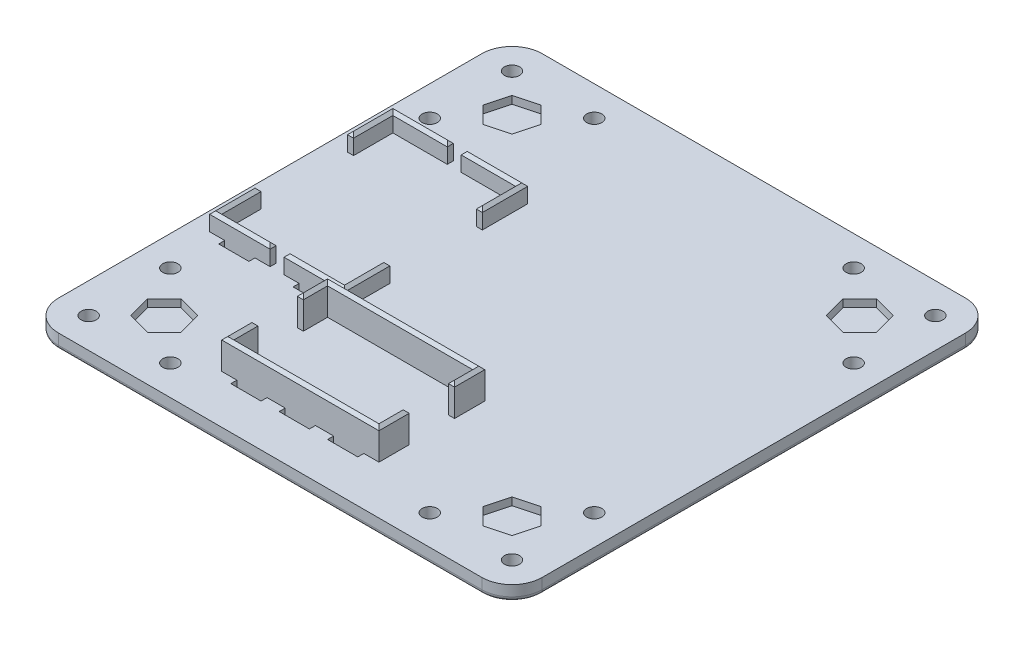
SolidWorks part; units mm, degrees
ref_plane "Front Plane" through (0, 0, 0) normal (0, 0, 1) x (1, 0, 0)
ref_plane "Top Plane" through (0, 0, 0) normal (0, 1, 0) x (1, 0, 0)
ref_plane "Right Plane" through (0, 0, 0) normal (1, 0, 0) x (0, 0, -1)
sketch "Sketch1" plane through (0, 0, 0) normal (0, 1, 0) x (1, 0, 0)
  line L1 (0, 0) -> (203.2, 0)
  line L2 (0, 0) -> (0, 203.2)
  line L3 (0, 203.2) -> (203.2, 203.2)
  line L4 (203.2, 0) -> (203.2, 203.2)
  dimension "D1" = 203.2
  dimension "D2" = 203.2
extrude "Boss-Extrude1" add sketch "Sketch1" along normal blind 6.35
fillet "Fillet1" radius 12.7 4 edges at (0, 3.175, -203.2) (0, 3.175, 0) (203.2, 3.175, 0) (203.2, 3.175, -203.2)
sketch "Sketch2" plane through (0, 0, 0) normal (0, -1, 0) x (1, 0, 0)
  circle A0 centre (12.7, -12.7) radius 3.175
  circle A1 centre (190.5, -12.7) radius 3.175
  circle A2 centre (190.5, -190.5) radius 3.175
  circle A3 centre (12.7, -190.5) radius 3.175
  arc A4 (190.5, -203.2) -> (203.2, -190.5) centre (190.5, -190.5) ccw construction
  arc A5 (12.7, 0) -> (0, -12.7) centre (12.7, -12.7) ccw construction
  dimension "D1" = 6.35
extrude "Cut-Extrude1" cut sketch "Sketch2" against normal through all
sketch "Sketch22" plane through (0, 6.35, 0) normal (0, 1, 0) x (1, 0, 0)
  line L17 (190.5, 203.2) -> (12.7, 203.2) construction
  line L18 (203.2, 12.7) -> (203.2, 190.5) construction
  line L21 (181.6542, 181.6542) -> (172.0521, 184.2271)
  line L22 (172.0521, 184.2271) -> (165.0229, 177.1979)
  line L23 (165.0229, 177.1979) -> (167.5958, 167.5958)
  line L24 (167.5958, 167.5958) -> (177.1979, 165.0229)
  line L25 (177.1979, 165.0229) -> (184.2271, 172.0521)
  line L26 (184.2271, 172.0521) -> (181.6542, 181.6542)
  line L27 (174.625, 174.625) -> (190.5, 190.5) construction
  line L28 (101.6, 203.2) -> (101.6, 0) construction
  line L29 (12.7, 0) -> (190.5, 0) construction
  line L30 (203.2, 101.6) -> (0, 101.6) construction
  line L31 (0, 190.5) -> (0, 12.7) construction
  line L32 (28.575, 174.625) -> (12.7, 190.5) construction
  line L33 (18.9729, 172.0521) -> (21.5458, 181.6542)
  line L34 (26.0021, 165.0229) -> (18.9729, 172.0521)
  line L35 (35.6042, 167.5958) -> (26.0021, 165.0229)
  line L36 (38.1771, 177.1979) -> (35.6042, 167.5958)
  line L37 (31.1479, 184.2271) -> (38.1771, 177.1979)
  line L38 (21.5458, 181.6542) -> (31.1479, 184.2271)
  line L39 (174.625, 28.575) -> (190.5, 12.7) construction
  line L40 (184.2271, 31.1479) -> (181.6542, 21.5458)
  line L41 (177.1979, 38.1771) -> (184.2271, 31.1479)
  line L42 (167.5958, 35.6042) -> (177.1979, 38.1771)
  line L43 (165.0229, 26.0021) -> (167.5958, 35.6042)
  line L44 (172.0521, 18.9729) -> (165.0229, 26.0021)
  line L45 (181.6542, 21.5458) -> (172.0521, 18.9729)
  line L46 (28.575, 28.575) -> (12.7, 12.7) construction
  line L47 (21.5458, 21.5458) -> (31.1479, 18.9729)
  line L48 (31.1479, 18.9729) -> (38.1771, 26.0021)
  line L49 (38.1771, 26.0021) -> (35.6042, 35.6042)
  line L50 (35.6042, 35.6042) -> (26.0021, 38.1771)
  line L51 (26.0021, 38.1771) -> (18.9729, 31.1479)
  line L52 (18.9729, 31.1479) -> (21.5458, 21.5458)
  circle A0 centre (174.625, 174.625) radius 8.609 construction
  circle A1 centre (28.575, 174.625) radius 8.609 construction
  circle A2 centre (174.625, 28.575) radius 8.609 construction
  circle A3 centre (28.575, 28.575) radius 8.609 construction
  dimension "D5" = 17.218
  dimension "D3" = 28.575
  dimension "D4" = 28.575
extrude "Cut-Extrude2" cut sketch "Sketch22" against normal blind 3.175
sketch "Sketch23" plane through (0, 6.35, 0) normal (0, 1, 0) x (1, 0, 0)
  line L1 (64.262, 145.542) -> (38.862, 145.542)
  line L2 (64.262, 145.542) -> (64.262, 126.492)
  line L3 (64.262, 68.58) -> (38.862, 68.58)
  line L4 (7.62, 145.542) -> (7.62, 126.492)
  line L5 (7.62, 145.542) -> (7.62, 203.2) construction
  line L6 (190.5, 203.2) -> (12.7, 203.2) construction
  line L7 (7.62, 68.58) -> (7.62, 0) construction
  line L8 (12.7, 0) -> (190.5, 0) construction
  line L9 (33.02, 145.542) -> (33.02, 143.002)
  line L10 (61.722, 143.002) -> (38.862, 143.002)
  line L11 (61.722, 143.002) -> (61.722, 126.492)
  line L12 (61.722, 71.12) -> (38.862, 71.12)
  line L13 (10.16, 143.002) -> (10.16, 126.492)
  line L14 (38.862, 145.542) -> (38.862, 143.002)
  line L15 (64.262, 126.492) -> (61.722, 126.492)
  line L16 (64.262, 87.63) -> (61.722, 87.63)
  line L17 (10.16, 126.492) -> (7.62, 126.492)
  line L18 (10.16, 87.63) -> (7.62, 87.63)
  line L19 (33.02, 71.12) -> (33.02, 68.58)
  line L20 (38.862, 71.12) -> (38.862, 68.58)
  line L21 (33.02, 145.542) -> (7.62, 145.542)
  line L22 (33.02, 143.002) -> (10.16, 143.002)
  line L23 (64.262, 87.63) -> (64.262, 68.58)
  line L24 (61.722, 87.63) -> (61.722, 71.12)
  line L25 (33.02, 71.12) -> (10.16, 71.12)
  line L26 (33.02, 68.58) -> (7.62, 68.58)
  line L27 (10.16, 87.63) -> (10.16, 71.12)
  line L28 (7.62, 87.63) -> (7.62, 68.58)
  line L29 (0, 190.5) -> (0, 12.7) construction
  point P32 (33.02, 144.272)
  dimension "D2" = 71.882
  dimension "D3" = 51.562
  dimension "D4" = 2.54
  dimension "D5" = 2.54
  dimension "D6" = 2.54
  dimension "D7" = 2.54
  dimension "D8" = 19.05
  dimension "D9" = 19.05
  dimension "D10" = 25.4
  dimension "D11" = 25.4
  dimension "D12" = 19.05
  dimension "D13" = 19.05
  dimension "D14" = 25.4
  dimension "D15" = 25.4
  dimension "D17" = 7.62
  dimension "D18" = 134.62
extrude "Boss-Extrude2" add sketch "Sketch23" along normal blind 7.62
chamfer "Chamfer1" distance 1.27 angle 45 24 edges at (8.89, 13.97, -87.63) (10.16, 13.97, -79.375) (21.59, 13.97, -71.12) (33.02, 13.97, -69.85) (20.32, 13.97, -68.58) (7.62, 13.97, -78.105) (51.562, 13.97, -68.58) (38.862, 13.97, -69.85) (50.292, 13.97, -71.12) (61.722, 13.97, -79.375) (62.992, 13.97, -87.63) (64.262, 13.97, -78.105) (62.992, 13.97, -126.492) (61.722, 13.97, -134.747) (50.292, 13.97, -143.002) (38.862, 13.97, -144.272) (51.562, 13.97, -145.542) (64.262, 13.97, -136.017) (33.02, 13.97, -144.272) (21.59, 13.97, -143.002) (10.16, 13.97, -134.747) (8.89, 13.97, -126.492) (7.62, 13.97, -136.017) (20.32, 13.97, -145.542)
sketch "Sketch24" plane through (0, 6.35, 0) normal (0, 1, 0) x (1, 0, 0)
  line L0 (12.7, 0) -> (190.5, 0) construction
  line L1 (124.46, 62.23) -> (63.5, 62.23)
  line L2 (124.46, 62.23) -> (124.46, 52.07)
  line L3 (124.46, 22.86) -> (63.5, 22.86)
  line L4 (63.5, 62.23) -> (63.5, 52.07)
  line L5 (0, 190.5) -> (0, 12.7) construction
  line L6 (127, 64.77) -> (60.96, 64.77)
  line L7 (127, 64.77) -> (127, 52.07)
  line L8 (127, 20.32) -> (60.96, 20.32)
  line L9 (60.96, 64.77) -> (60.96, 52.07)
  line L10 (60.96, 52.07) -> (63.5, 52.07)
  line L11 (60.96, 33.02) -> (63.5, 33.02)
  line L12 (60.96, 33.02) -> (60.96, 20.32)
  line L13 (63.5, 33.02) -> (63.5, 22.86)
  line L14 (124.46, 52.07) -> (127, 52.07)
  line L15 (124.46, 33.02) -> (127, 33.02)
  line L16 (124.46, 33.02) -> (124.46, 22.86)
  line L17 (127, 33.02) -> (127, 20.32)
  dimension "D1" = 39.37
  dimension "D2" = 60.96
  dimension "D3" = 22.86
  dimension "D4" = 2.54
  dimension "D5" = 2.54
  dimension "D6" = 2.54
  dimension "D7" = 2.54
  dimension "D8" = 63.5
  dimension "D9" = 12.7
  dimension "D10" = 12.7
extrude "Boss-Extrude3" add sketch "Sketch24" along normal blind 12.7
chamfer "Chamfer2" distance 1.27 angle 45 16 edges at (93.98, 19.05, -62.23) (63.5, 19.05, -57.15) (62.23, 19.05, -52.07) (60.96, 19.05, -58.42) (93.98, 19.05, -64.77) (127, 19.05, -58.42) (93.98, 19.05, -20.32) (60.96, 19.05, -26.67) (62.23, 19.05, -33.02) (63.5, 19.05, -27.94) (93.98, 19.05, -22.86) (124.46, 19.05, -57.15) (125.73, 19.05, -52.07) (124.46, 19.05, -27.94) (125.73, 19.05, -33.02) (127, 19.05, -26.67)
fillet "Fillet2" radius 1.905 12 edges at (3.7197, 0, -3.7197) (101.6, 0, 0) (199.4803, 0, -3.7197) (203.2, 0, -101.6) (199.4803, 0, -199.4803) (101.6, 0, -203.2) (3.7197, 0, -199.4803) (0, 0, -101.6) (12.7, 0, -15.875) (190.5, 0, -15.875) (190.5, 0, -193.675) (12.7, 0, -193.675)
sketch "Sketch27" plane through (0, 6.35, 0) normal (0, 1, 0) x (1, 0, 0)
  line L0 (38.862, 143.002) -> (61.722, 143.002) construction
  line L1 (85.852, 143.002) -> (137.414, 143.002)
  line L2 (85.852, 143.002) -> (85.852, 129.032)
  line L3 (85.852, 71.12) -> (137.414, 71.12)
  line L4 (137.414, 143.002) -> (137.414, 129.032)
  line L5 (83.312, 145.542) -> (83.312, 129.032)
  line L6 (83.312, 68.58) -> (139.954, 68.58)
  line L7 (139.954, 145.542) -> (139.954, 129.032)
  line L8 (83.312, 145.542) -> (139.954, 145.542)
  line L9 (83.312, 129.032) -> (85.852, 129.032)
  line L10 (83.312, 90.17) -> (85.852, 90.17)
  line L11 (137.414, 90.17) -> (139.954, 90.17)
  line L12 (139.954, 129.032) -> (137.414, 129.032)
  line L13 (83.312, 90.17) -> (83.312, 68.58)
  line L14 (83.312, 145.542) -> (83.312, 68.58) construction
  line L15 (85.852, 90.17) -> (85.852, 71.12)
  line L16 (85.852, 143.002) -> (85.852, 71.12) construction
  line L17 (137.414, 90.17) -> (137.414, 71.12)
  line L18 (137.414, 143.002) -> (137.414, 71.12) construction
  line L19 (139.954, 90.17) -> (139.954, 68.58)
  line L20 (139.954, 145.542) -> (139.954, 68.58) construction
  line L21 (64.262, 68.58) -> (64.262, 87.63) construction
  dimension "D1" = 71.882
  dimension "D2" = 51.562
  dimension "D4" = 19.05
  dimension "D3" = 2.54
sketch "Sketch28" plane through (0, 6.35, 0) normal (0, 1, 0) x (1, 0, 0)
  line L0 (190.5, 203.2) -> (12.7, 203.2) construction
  line L1 (203.2, 12.7) -> (203.2, 190.5) construction
  line L2 (12.7, 0) -> (190.5, 0) construction
  line L4 (0, 190.5) -> (0, 12.7) construction
  circle A0 centre (47.117, 190.627) radius 3.175
  circle A1 centre (156.083, 190.627) radius 3.175
  circle A2 centre (190.627, 156.083) radius 3.175
  circle A3 centre (190.627, 47.117) radius 3.175
  circle A4 centre (156.083, 12.573) radius 3.175
  circle A5 centre (47.117, 12.573) radius 3.175
  circle A6 centre (12.573, 156.083) radius 3.175
  circle A7 centre (12.573, 47.117) radius 3.175
  dimension "D4" = 6.35
  dimension "D1" = 12.573
  dimension "D2" = 12.573
  dimension "D3" = 12.573
  dimension "D5" = 12.573
  dimension "D6" = 47.117
  dimension "D7" = 47.117
  dimension "D8" = 47.117
  dimension "D9" = 47.117
extrude "Cut-Extrude3" cut sketch "Sketch28" against normal through all
sketch "Sketch29" plane through (0, 6.35, 0) normal (0, 1, 0) x (1, 0, 0)
  line L0 (33.02, 145.542) -> (7.62, 145.542) construction
  line L1 (13.97, 145.542) -> (26.67, 145.542)
  line L2 (13.97, 145.542) -> (13.97, 148.082)
  line L3 (13.97, 148.082) -> (26.67, 148.082)
  line L4 (26.67, 145.542) -> (26.67, 148.082)
  line L5 (64.262, 145.542) -> (38.862, 145.542) construction
  line L6 (45.212, 145.542) -> (57.912, 145.542)
  line L7 (45.212, 145.542) -> (45.212, 148.082)
  line L8 (45.212, 148.082) -> (57.912, 148.082)
  line L9 (57.912, 145.542) -> (57.912, 148.082)
  line L10 (127, 64.77) -> (60.96, 64.77) construction
  line L11 (67.31, 64.77) -> (80.01, 64.77)
  line L12 (67.31, 64.77) -> (67.31, 67.31)
  line L13 (67.31, 67.31) -> (80.01, 67.31)
  line L14 (80.01, 64.77) -> (80.01, 67.31)
  line L15 (60.96, 20.32) -> (127, 20.32) construction
  line L16 (107.95, 64.77) -> (120.65, 64.77)
  line L17 (107.95, 64.77) -> (107.95, 67.31)
  line L18 (107.95, 67.31) -> (120.65, 67.31)
  line L19 (120.65, 64.77) -> (120.65, 67.31)
  line L20 (67.31, 20.32) -> (80.01, 20.32)
  line L21 (67.31, 20.32) -> (67.31, 17.78)
  line L22 (67.31, 17.78) -> (80.01, 17.78)
  line L23 (80.01, 20.32) -> (80.01, 17.78)
  line L25 (107.95, 20.32) -> (120.65, 20.32)
  line L26 (107.95, 20.32) -> (107.95, 17.78)
  line L27 (107.95, 17.78) -> (120.65, 17.78)
  line L28 (120.65, 20.32) -> (120.65, 17.78)
  line L33 (38.862, 68.58) -> (64.262, 68.58) construction
  line L34 (45.212, 68.58) -> (57.912, 68.58)
  line L35 (45.212, 68.58) -> (45.212, 66.04)
  line L36 (45.212, 66.04) -> (57.912, 66.04)
  line L37 (57.912, 68.58) -> (57.912, 66.04)
  line L40 (33.02, 145.542) -> (33.02, 143.002) construction
  line L41 (38.862, 143.002) -> (38.862, 145.542) construction
  line L42 (38.862, 71.12) -> (38.862, 68.58) construction
  line L44 (7.62, 68.58) -> (33.02, 68.58) construction
  line L45 (13.97, 68.58) -> (26.67, 68.58)
  line L46 (13.97, 68.58) -> (13.97, 66.04)
  line L47 (13.97, 66.04) -> (26.67, 66.04)
  line L48 (26.67, 68.58) -> (26.67, 66.04)
  line L49 (33.02, 68.58) -> (33.02, 71.12) construction
  line L50 (60.96, 64.77) -> (60.96, 52.07) construction
  line L51 (60.96, 33.02) -> (60.96, 20.32) construction
  line L52 (127, 20.32) -> (127, 33.02) construction
  line L53 (127, 64.77) -> (127, 52.07) construction
  line L54 (60.96, 64.77) -> (127, 64.77) construction
  line L55 (87.63, 64.77) -> (100.33, 64.77)
  line L56 (87.63, 64.77) -> (87.63, 67.31)
  line L57 (87.63, 67.31) -> (100.33, 67.31)
  line L58 (100.33, 64.77) -> (100.33, 67.31)
  line L59 (127, 20.32) -> (60.96, 20.32) construction
  line L60 (100.33, 20.32) -> (87.63, 20.32)
  line L61 (100.33, 20.32) -> (100.33, 17.78)
  line L62 (100.33, 17.78) -> (87.63, 17.78)
  line L63 (87.63, 20.32) -> (87.63, 17.78)
  line L64 (63.5, 62.23) -> (124.46, 62.23) construction
  line L65 (124.46, 22.86) -> (63.5, 22.86) construction
  point P75 (93.98, 67.31)
  point P78 (93.98, 62.23)
  point P79 (93.98, 17.78)
  point P82 (93.98, 22.86)
  dimension "D1" = 12.7
  dimension "D2" = 2.54
  dimension "D3" = 6.35
  dimension "D4" = 6.35
  dimension "D5" = 6.35
  dimension "D6" = 6.35
  dimension "D7" = 6.35
  dimension "D8" = 6.35
  dimension "D9" = 6.35
  dimension "D10" = 6.35
  dimension "D11" = 2.54
extrude "Cut-Extrude4" cut sketch "Sketch29" against normal through all
